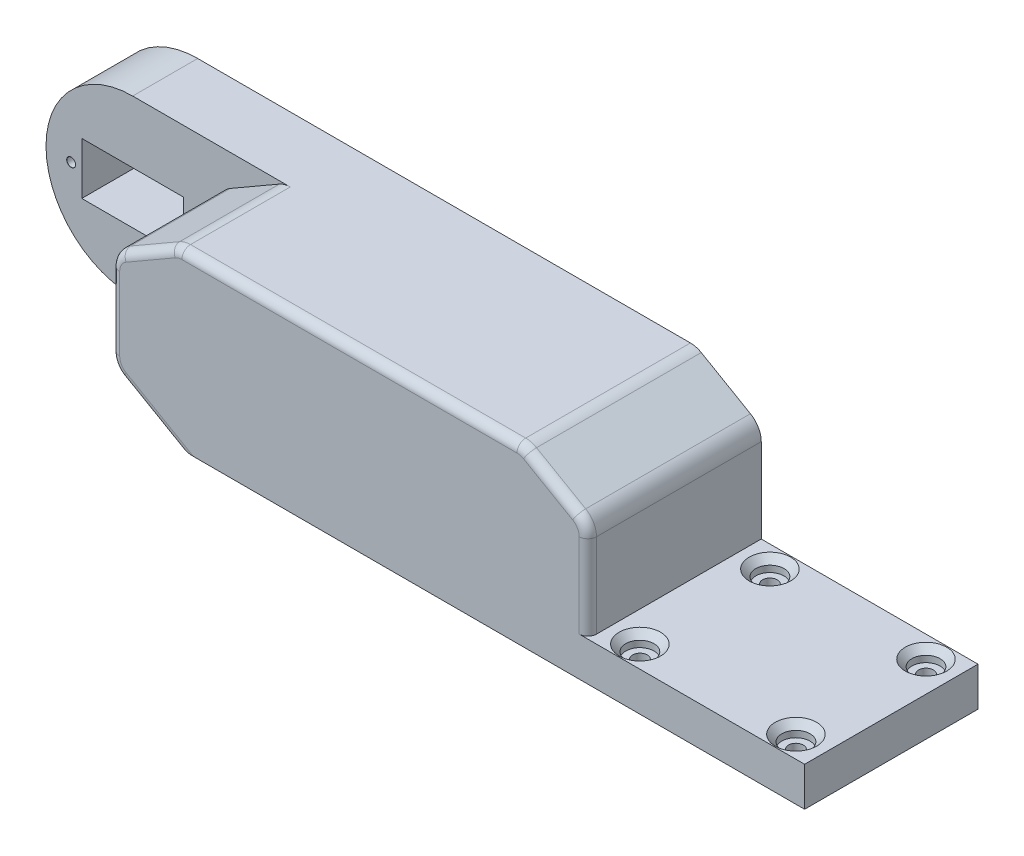
SolidWorks part; units mm, degrees
ref_plane "Front Plane" through (0, 0, 0) normal (0, 0, 1) x (1, 0, 0)
ref_plane "Top Plane" through (0, 0, 0) normal (0, 1, 0) x (1, 0, 0)
ref_plane "Right Plane" through (0, 0, 0) normal (1, 0, 0) x (0, 0, -1)
sketch "Sketch9" plane through (0, 0, 0) normal (0, 0, 1) x (1, 0, 0)
  point P0 (-186, 0)
  point P1 (0, 0)
  point P3 (0, 0)
  point P4 (0, 0)
  dimension "D1" = 186
sketch "Sketch1" plane through (0, 0, 0) normal (0, 0, 1) x (1, 0, 0)
  line L0 (0, 0) -> (-200, 0)
  line L1 (-200, 0) -> (-200, 40)
  line L2 (-200, 40) -> (-50, 40)
  line L3 (0, 9) -> (0, 0)
  line L4 (0, 9) -> (-50, 9)
  line L5 (-50, 9) -> (-50, 40)
  dimension "D1" = 150
  dimension "D2" = 40
  dimension "D3" = 9
  dimension "D4" = 50
extrude "Boss-Extrude1" add sketch "Sketch1" along normal blind 40
sketch "Sketch5" plane through (0, 0, 40) normal (0, 0, 1) x (1, 0, 0)
  line L0 (-200, 0) -> (0, 0) construction
  line L1 (-145, 40) -> (-160, 31.3397)
  line L2 (-160, 31.3397) -> (-160, 8.6603)
  line L3 (-160, 8.6603) -> (-145, 0)
  line L7 (-50, 40) -> (-200, 40) construction
  line L8 (-145, 40) -> (-200, 40)
  line L9 (-200, 40) -> (-200, 0)
  line L10 (-200, 0) -> (-145, 0)
  line L12 (-120.718, 16.2277) -> (-120.718, 26.2277) [skipped]
  line L13 (-133.8054, 1.1042) -> (-125.1452, 6.1042) [skipped]
  line L14 (-124.2584, 33.3838) -> (-132.9187, 38.3838) [skipped]
  circle A0 centre (-140.359, 20) radius 19.641 construction
  point P1 (0, 0)
  dimension "D1" = 40
  dimension "D2" = 15
extrude "Cut-Extrude2" cut sketch "Sketch5" against normal blind 25
sketch "Sketch13" plane through (0, 0, 40) normal (0, 0, 1) x (1, 0, 0)
  line L0 (-50, 9) -> (-50, 40) construction
  line L1 (-50, 8.6603) -> (-50, 31.3397) construction
  line L2 (-50, 31.3397) -> (-65, 40)
  line L6 (-65, 0) -> (-50, 8.6603) construction
  line L7 (-145, 0) -> (0, 0) construction
  line L8 (-50, 40) -> (-145, 40) construction
  line L9 (-65, 40) -> (-50, 40)
  line L10 (-50, 40) -> (-50, 31.3397)
  line L11 (-87.5417, 7.6554) -> (-78.8814, 2.6554) [skipped]
  line L12 (-89.282, 30) -> (-89.282, 20) [skipped]
  line L13 (-70.2211, 42.3446) -> (-78.8814, 37.3446) [skipped]
  line L14 (-160, 8.6603) -> (-160, 31.3397) construction
  line L15 (-160, 31.3397) -> (-145, 40) construction
  circle A0 centre (-69.641, 20) radius 19.641 construction
extrude "Cut-Extrude4" cut sketch "Sketch13" against normal through all
hole_wizard "Ø2.0mm Dowel Hole1" positions "Sketch6" profile "Sketch7" hole size "Ø2.0" standard "AS"
sketch "Sketch6" plane through (0, 0, 15) normal (0, 0, 1) x (1, 0, 0)
  point P0 (-194.2, 19.6644)
  point P2 (-165.8, 19.6644)
  dimension "D1" = 28.4
  dimension "D2" = 8.2
sketch "Sketch7" plane through (-194.2, 19.6644, 15) normal (1, 0, 0) x (0, -1, 0)
  line L0 (0, 0) -> (0, 9.6009)
  line L1 (0, 9.6009) -> (1, 9)
  line L2 (1, 9) -> (1, 0.025)
  line L3 (1, 0.025) -> (1.025, 0)
  line L5 (1.025, 0) -> (0, 0)
  line L6 (-1, 0.025) -> (-1.025, 0) construction
  line L10 (0, 9.6009) -> (-1, 9) construction
  line L11 (0, -6.35) -> (0, 107.95) construction
  dimension "Hole Dia." = 2
  dimension "Hole Depth" = 9
  dimension "Near C'Sink Dia." = 2.05
  dimension "Near C'Sink Angle" = 90
  dimension "Drill Angle" = 118
sketch "Sketch11" plane through (0, 0, 15) normal (0, 0, 1) x (1, 0, 0)
  line L0 (-194.2, 19.6644) -> (-165.8, 19.6644) construction
  line L1 (-191.75, 25.6644) -> (-168.25, 25.6644) construction
  line L3 (-191.75, 13.6644) -> (-168.25, 13.6644)
  line L4 (-168.25, 25.6644) -> (-168.25, 13.6644)
  line L5 (-191.75, 25.6644) -> (-168.25, 25.6644)
  line L6 (-191.75, 25.6644) -> (-191.75, 19.6644) construction
  line L7 (-191.75, 19.6644) -> (-191.75, 13.6644) construction
  line L8 (-191.75, 25.6644) -> (-191.75, 13.6644)
  point P6 (0, 0)
  point P9 (-180, 19.6644)
  point P17 (-180, 25.6644)
  dimension "D1" = 23.5
  dimension "D2" = 12
extrude "Cut-Extrude3" cut sketch "Sketch11" against normal through all
fillet "Fillet7" radius 5 5 edges at (-160, 8.6603, 27.5) (-145, 40, 27.5) (-160, 31.3397, 27.5) (-65, 40, 20) (-50, 31.3397, 20)
fillet "Fillet6" radius 2 11 edges at (-151.25, 3.6084, 40) (-160, 20, 40) (-151.8301, 36.0566, 40) (-50, 18.7265, 40) (-58.1699, 36.0566, 40) (-159.3301, 9.047, 40) (-159.3301, 30.953, 40) (-50.6699, 30.953, 40) (-65.0457, 39.8296, 40) (-105, 40, 40) (-144.9543, 39.8296, 40)
hole_wizard "CBORE for M5 Cheese Head Screw1" positions "Sketch2" profile "Sketch3" counterbore size "M5" standard "AS" end condition through all
sketch "Sketch2" plane through (0, 9, 0) normal (0, 1, 0) x (1, 0, 0)
  line L0 (-50, -5) -> (-43, -5) construction
  line L1 (-50, -38) -> (-50, 0) construction
  line L3 (-7, -5) -> (0, -5) construction
  line L4 (0, -40) -> (0, 0) construction
  line L6 (-7, -5) -> (-7, 0)
  line L7 (0, 0) -> (-50, 0) construction
  line L11 (-7, -35) -> (-7, -40) construction
  line L12 (0, -40) -> (-52, -40) construction
  point P0 (-43, -5)
  point P2 (-7, -5)
  point P4 (-43, -35)
  point P6 (-7, -35)
  point P43 (-40, -5)
  point P44 (0, 0)
  dimension "D1" = 36
  dimension "D2" = 30
sketch "Sketch3" plane through (-43, 9, 5) normal (1, 0, 0) x (0, 0, 1)
  line L0 (0, 0) -> (0, 9)
  line L1 (0, 9) -> (1.7, 9)
  line L3 (1.7, 9) -> (1.7, 3)
  line L4 (3.25, 3) -> (1.7, 3)
  line L5 (3.25, 3) -> (3.25, 1.525)
  line L6 (3.25, 1.525) -> (4.775, 0)
  line L7 (4.775, 0) -> (0, 0)
  line L8 (-3.25, 1.525) -> (-4.775, 0) construction
  line L11 (0, -6.35) -> (0, 107.95) construction
  dimension "Thru Hole Dia." = 3.4
  dimension "Thru Hole Depth" = 9
  dimension "C'Bore Dia." = 6.5
  dimension "C'Bore Depth" = 3
  dimension "Near C'Sink Dia." = 9.55
  dimension "Near C'Sink Angle" = 90
fillet "Fillet8" radius 20 2 edges at (-200, 0, 7.5) (-200, 40, 7.5)
